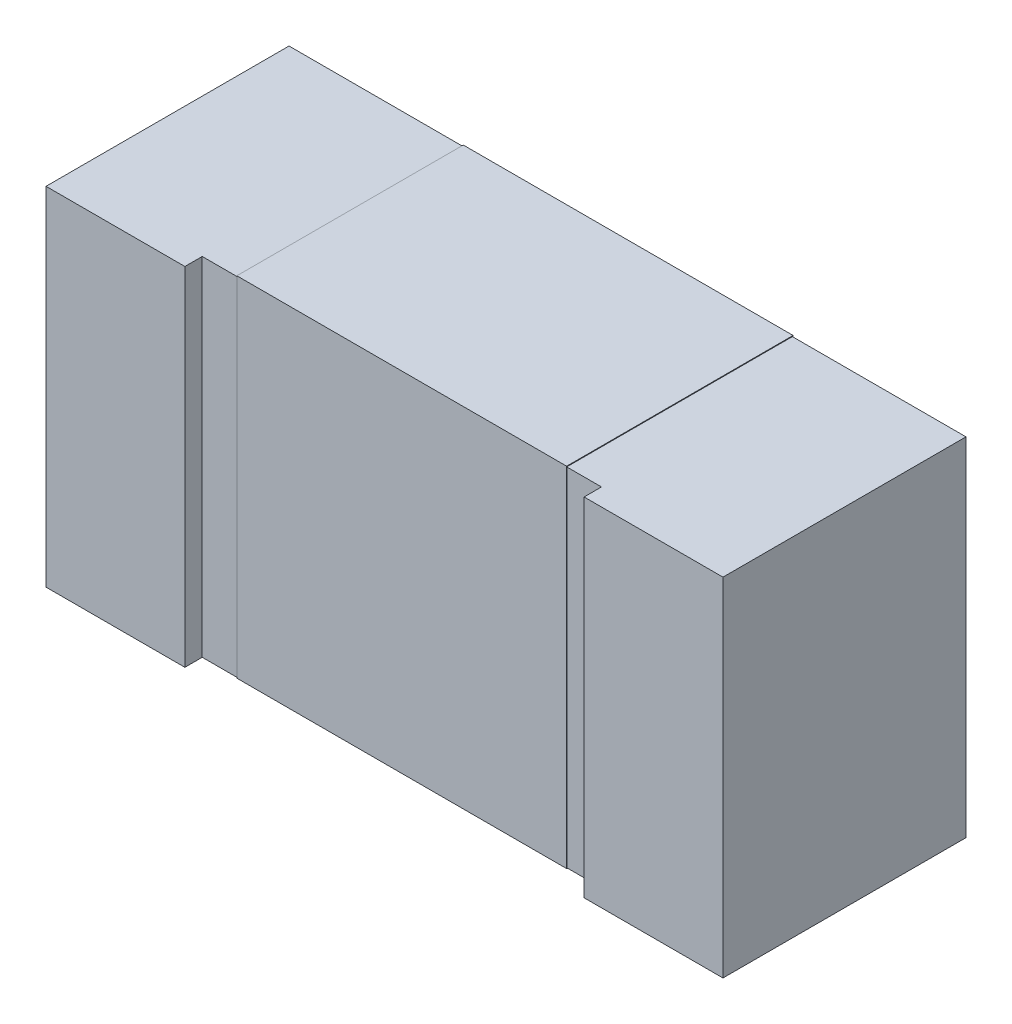
SolidWorks part; units mm, degrees
ref_plane "Front Plane" through (0, 0, 0) normal (0, 0, 1) x (1, 0, 0)
ref_plane "Top Plane" through (0, 0, 0) normal (0, 1, 0) x (1, 0, 0)
ref_plane "Right Plane" through (0, 0, 0) normal (1, 0, 0) x (0, 0, -1)
sketch "Sketch2" plane through (0, 0, 0) normal (0, 1, 0) x (0, 0, -1)
  line L0 (0, 0.2413) -> (-0.0254, 0.2413)
  line L1 (-0.0254, 0.2413) -> (-0.0254, 0.4699)
  line L2 (-0.0254, 0.4699) -> (-0.3302, 0.4699)
  line L3 (-0.3302, 0.4699) -> (-0.3302, 0.2921)
  line L4 (0, -0.4953) -> (0, -0.2413)
  line L5 (-0.3302, 0.2921) -> (-0.3556, 0.2921)
  line L6 (-0.3556, 0.2921) -> (-0.3556, 0.4953)
  line L7 (-0.3556, 0.4953) -> (0, 0.4953)
  line L8 (0, 0.4953) -> (0, 0.2413)
  line L9 (-0.3312, 0) -> (0.2179, 0) construction
  line L10 (-0.3556, -0.4953) -> (0, -0.4953)
  line L11 (-0.3556, -0.2921) -> (-0.3556, -0.4953)
  line L12 (-0.3302, -0.2921) -> (-0.3556, -0.2921)
  line L13 (-0.3302, -0.4699) -> (-0.3302, -0.2921)
  line L14 (-0.0254, -0.4699) -> (-0.3302, -0.4699)
  line L15 (-0.0254, -0.2413) -> (-0.0254, -0.4699)
  line L16 (0, -0.2413) -> (-0.0254, -0.2413)
  dimension "D1" = 0.254
  dimension "D2" = 0.3556
  dimension "D3" = 0.2032
  dimension "D4" = 0.0254
  dimension "D5" = 0.0254
  dimension "D6" = 0.0254
  dimension "D7" = 0.4953
extrude "Boss-Extrude1" add sketch "Sketch2" along normal mid plane 0.508
sketch "Sketch3" plane through (0, 0.254, 0) normal (0, 1, 0) x (1, 0, 0)
  line L1 (-0.4699, -0.0254) -> (0.4699, -0.0254)
  line L2 (-0.4699, -0.0254) -> (-0.4699, -0.3302)
  line L3 (-0.4699, -0.3302) -> (0.4699, -0.3302)
  line L4 (0.4699, -0.0254) -> (0.4699, -0.3302)
extrude "Boss-Extrude2" add sketch "Sketch3" against normal blind 0.508
sketch "Sketch4" plane through (0.2413, 0, 0) normal (-1, 0, 0) x (0, 0, 1)
  line L0 (0, 0.254) -> (0.3556, 0.254) construction
  line L1 (-0.001, 0.255) -> (0.3304, 0.255)
  line L2 (-0.001, 0.255) -> (-0.001, -0.255)
  line L3 (-0.001, -0.255) -> (0.3304, -0.255)
  line L4 (0.3304, 0.255) -> (0.3304, -0.255)
  line L5 (0, 0.254) -> (0, -0.254) construction
  line L6 (0, -0.254) -> (0.3556, -0.254) construction
  dimension "D1" = 0.001
  dimension "D2" = 0.001
  dimension "D3" = 0.001
extrude "Boss-Extrude3" add sketch "Sketch4" along normal up to surface (0.4826 mm away) up to face at (-0.2413, 0, 0.0127)
